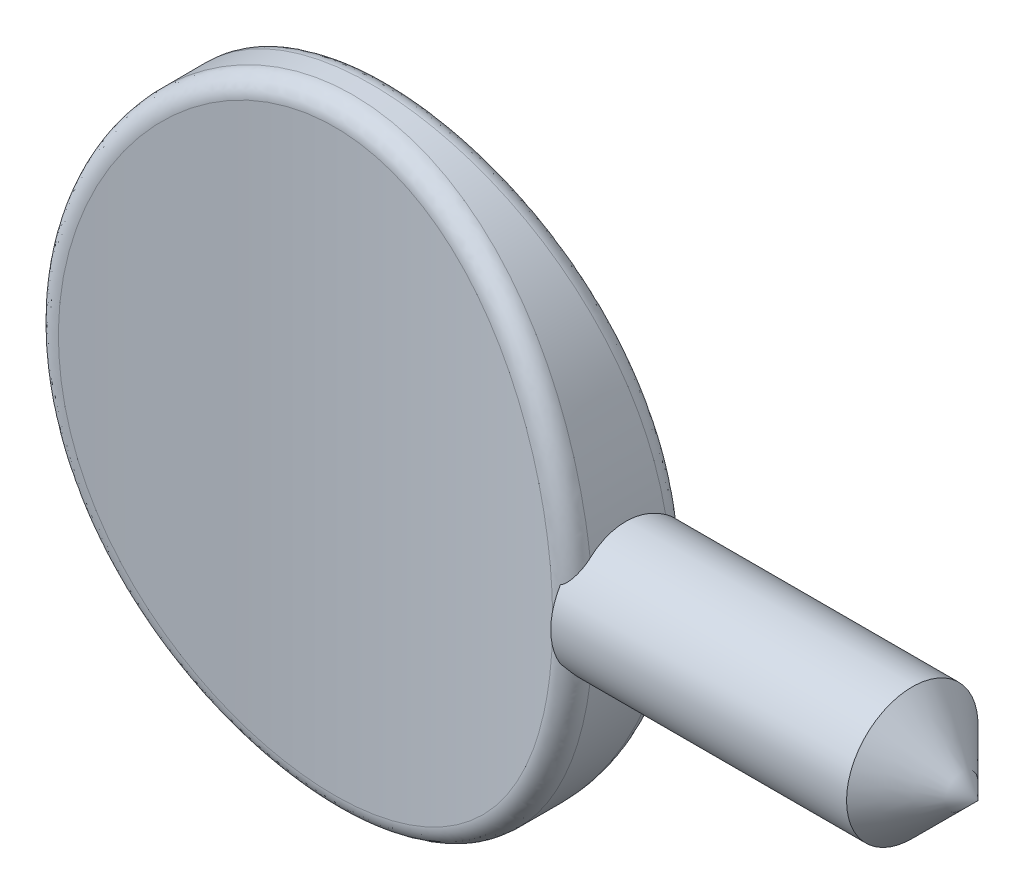
SolidWorks part; units mm, degrees
ref_plane "Front" through (0, 0, 0) normal (0, 0, 1) x (1, 0, 0)
ref_plane "Top" through (0, 0, 0) normal (0, 1, 0) x (1, 0, 0)
ref_plane "Right" through (0, 0, 0) normal (1, 0, 0) x (0, 0, -1)
ref_axis "Axis1" through (-50, 0, 0) along (1, 0, 0)
sketch "Sketch1" plane through (0, 0, 0) normal (0, 0, 1) x (1, 0, 0)
  line L0 (0, 0) -> (22.606, 0) construction
  line L1 (13.208, -2.413) -> (13.208, 2.413)
  line L2 (13.208, -2.413) -> (9.6776, -2.413) construction
  ellipse E0 centre (0, 0) end of major axis (0, -11.303) minor radius 9.906
  dimension "D2" = 3.302
  dimension "B" = 19.812
  dimension "L" = 12.7
extrude "Extrude1" add sketch "Sketch1" along normal mid plane 4.572
sketch "Sketch2" plane through (0, 0, 0) normal (0, 1, 0) x (1, 0, 0)
  line L0 (9.906, 2.286) -> (-9.906, 2.286) construction
  line L1 (0, 0) -> (0, 1.1721) construction
  line L2 (-1.7991, 0) -> (2.0444, 0) construction
  line L3 (-9.906, -2.286) -> (9.906, -2.286) construction
  line L6 (-9.906, 2.286) -> (-9.906, -2.286)
  line L7 (9.906, 2.286) -> (9.906, -2.286)
  arc A0 (-9.906, 2.286) -> (9.906, 2.286) centre (0, 40.2844) ccw
  arc A1 (-9.906, -2.286) -> (9.906, -2.286) centre (0, -40.2844) cw
extrude "Cut-Extrude1" cut sketch "Sketch2" against normal through all and the other way through all flip side to cut
fillet "Fillet3" radius 0.6773 2 edges at (-9.9037, -0.2444, 2.2854) (2.9825, 10.7785, -1.1294)
sketch "Sketch3" plane through (0, 0, 0) normal (0, 1, 0) x (1, 0, 0)
  line L0 (20.193, 2.413) -> (22.606, 0)
  line L1 (0, 0) -> (21.0288, 0) construction
  line L2 (0, 0) -> (22.606, 0) construction
  line L3 (13.208, 2.413) -> (13.208, 0) construction
  line L4 (13.208, 2.413) -> (20.193, 2.413)
  line L6 (13.208, 2.413) -> (9.3367, 2.413)
  line L7 (9.0722, 2.0783) -> (9.0722, 0)
  line L8 (9.3367, 0) -> (9.3367, 2.413) construction
  line L9 (9.0722, 0) -> (22.606, 0)
  arc A0 (9.3367, 2.413) -> (9.0722, 2.0783) centre (8.9927, 2.413) cw
  arc A3 (-9.906, 2.286) -> (9.906, 2.286) centre (0, 40.2844) ccw construction
  dimension "D1" = 45
revolve "Revolve1" add sketch "Sketch3" angle 360 about L0
cosmetic thread "Cosmetic Thread1" [suppressed]
sketch "Sketch4" plane through (0, 0, 0) normal (0, 0, 1) x (1, 0, 0)
  line L0 (0, 0) -> (27.7993, 0) construction
  line L1 (20.0097, 2.413) -> (20.193, 2.0955)
  line L2 (20.193, 2.0955) -> (20.3763, 2.413)
  line L3 (20.3763, 2.413) -> (20.3763, 2.7796)
  line L4 (20.3763, 2.7796) -> (20.0097, 2.7796)
  line L5 (20.0097, 2.7796) -> (20.0097, 2.413)
  line L6 (20.193, 2.413) -> (20.193, -2.413) construction
  dimension "D1" = 4.191
  dimension "D2" = 4.826
revolve "Cut-Revolve10" [suppressed] cut sketch "Sketch4" angle 360 about L0
pattern_linear "LPattern10" [suppressed] count 20 along (-1, 0, 0) of bodies 109
equation "\"D2@Sketch1\" = \"B@Sketch1\" / 6"
equation "\"D1@Fillet3\" = \"C1@Sketch2\" / 3"
equation "\"DIA@Sketch3\" = \"D@Sketch1\""
equation "\"D1@Cosmetic Thread1\" = \"L@Sketch1\" - \"D@Sketch1\" / 2"
equation "\"D1@Sketch4\" = \"D2@Cosmetic Thread1\""
equation "\"D2@Sketch4\" = \"DIA@Sketch3\""
equation "\"D1@LPattern10\" = \"D1@Cosmetic Thread1\" / \"P@LPattern10\" "
